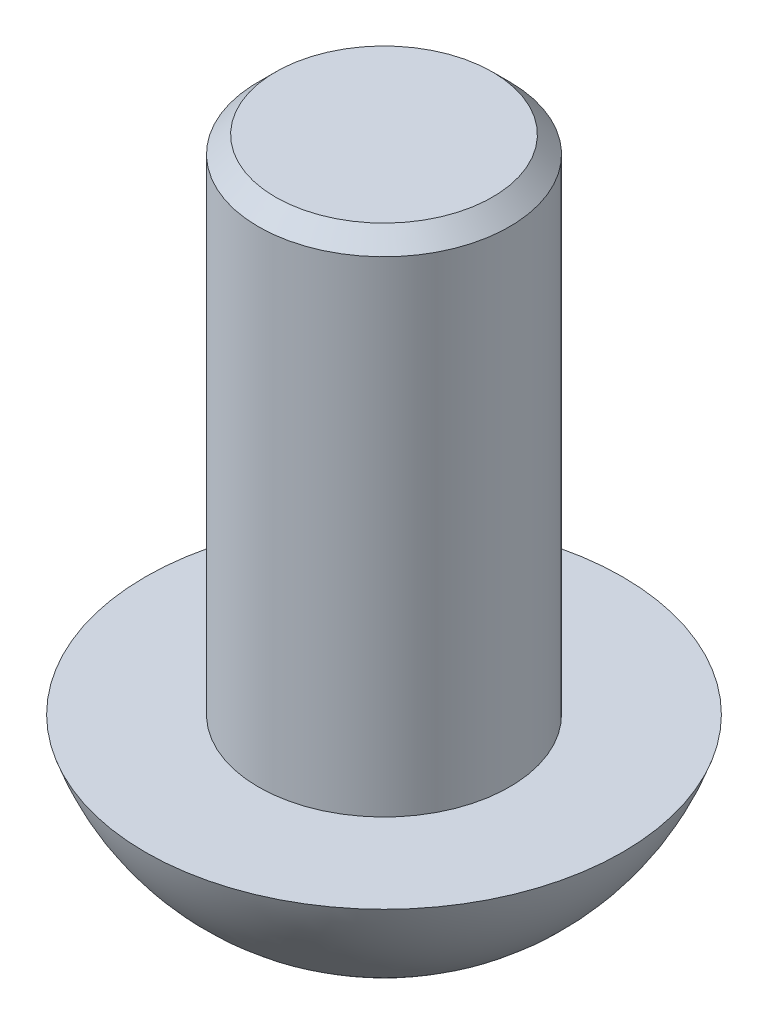
SolidWorks part; units mm, degrees
material "AISI 304"
ref_plane "前视基准面" through (0, 0, 0) normal (0, 0, 1) x (1, 0, 0)
ref_plane "上视基准面" through (0, 0, 0) normal (0, 1, 0) x (1, 0, 0)
ref_plane "右视基准面" through (0, 0, 0) normal (1, 0, 0) x (0, 0, -1)
other "Configuration Table"
sketch "草图1" plane through (0, 0, 0) normal (0, 0, 1) x (1, 0, 0)
  line L0 (2.5, 0) -> (2.5, 9.66)
  line L1 (2.16, 10) -> (-2.16, 10)
  line L2 (-2.5, 9.66) -> (-2.5, 0)
  line L3 (-2.5, 0) -> (-4.75, 0)
  line L4 (2.5, 0) -> (4.75, 0)
  line L6 (-2.5, -2.75) -> (-1.5, -2.75)
  line L7 (-1.5, -2.75) -> (-1.5, -0.75)
  line L8 (-1.5, -0.75) -> (0, 0)
  line L9 (0, 0) -> (1.5, -0.75)
  line L10 (1.5, -0.75) -> (1.5, -2.75)
  line L11 (1.5, -2.75) -> (2.5, -2.75)
  line L12 (0, 0) -> (0, 50000) construction
  line L13 (-2.5, 9.66) -> (-2.16, 10)
  line L14 (2.16, 10) -> (2.5, 9.66)
  arc A0 (-4.75, 0) -> (-2.5, -2.75) centre (0, 1.5909) ccw
  arc A1 (4.75, 0) -> (2.5, -2.75) centre (0, 1.5909) cw
  point P11 (0, 10)
  dimension "D3" = 4.32
  dimension "D1" = 5
  dimension "dl" = 5
  dimension "D2" = 45
  dimension "Dk" = 9.5
  dimension "k" = 2.75
  dimension "s" = 3
  dimension "t" = 2
  dimension "L" = 10
revolve "旋转2" add sketch "草图1" angle 360 about L12 region at (1.5602, 3.6277, 0)
sketch "草图2" plane through (0, -2.75, 0) normal (0, -1, 0) x (1, 0, 0)
  line L1 (1.7321, 0) -> (0.866, 1.5)
  line L2 (0.866, 1.5) -> (-0.866, 1.5)
  line L3 (-0.866, 1.5) -> (-1.7321, 0)
  line L4 (-1.7321, 0) -> (-0.866, -1.5)
  line L5 (-0.866, -1.5) -> (0.866, -1.5)
  line L6 (0.866, -1.5) -> (1.7321, 0)
  circle A0 centre (0, 0) radius 1.5 construction
  circle A1 centre (0, 0) radius 1.5 construction
extrude "切除-拉伸1" cut sketch "草图2" against normal up to surface (1.884 mm away) up to face at (0, -0.75, -1.5)
